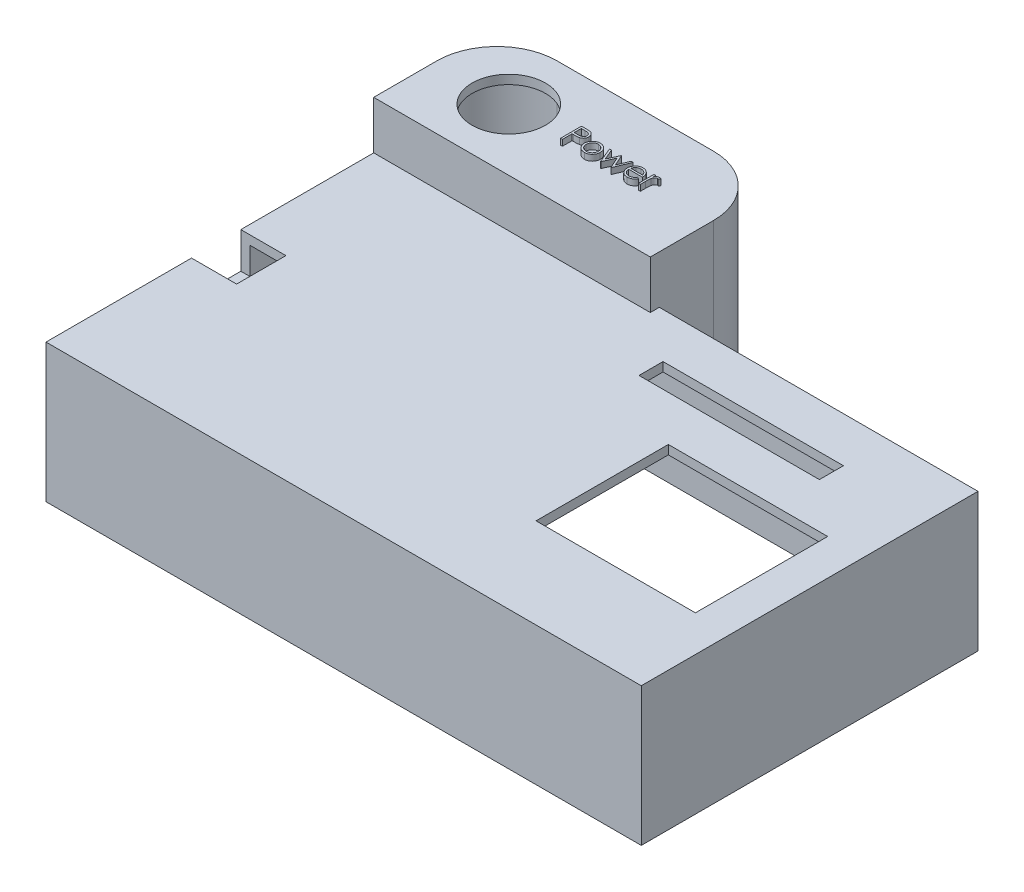
SolidWorks part; units mm, degrees
ref_plane "Front Plane" through (0, 0, 0) normal (0, 0, 1) x (1, 0, 0)
ref_plane "Top Plane" through (0, 0, 0) normal (0, 1, 0) x (1, 0, 0)
ref_plane "Right Plane" through (0, 0, 0) normal (1, 0, 0) x (0, 0, -1)
sketch "Sketch1" plane through (0, 0, 0) normal (0, 1, 0) x (1, 0, 0)
  line L1 (49.5, -28) -> (-49.5, -28)
  line L2 (49.5, -28) -> (49.5, 28)
  line L3 (49.5, 28) -> (-49.5, 28)
  line L4 (-49.5, -28) -> (-49.5, 28)
  line L5 (49.5, -28) -> (-49.5, 28) construction
  line L6 (49.5, 28) -> (-49.5, -28) construction
  point P0 (0, 0)
  dimension "D1" = 56
  dimension "D2" = 99
extrude "Boss-Extrude1" add sketch "Sketch1" along normal blind 23
sketch "Sketch3" plane through (0, 0, 0) normal (0, -1, 0) x (1, 0, 0)
  line L1 (-48, 26.5) -> (48, 26.5)
  line L2 (-48, 26.5) -> (-48, -26.5)
  line L3 (-48, -26.5) -> (48, -26.5)
  line L4 (48, 26.5) -> (48, -26.5)
  line L5 (-48, 26.5) -> (48, -26.5) construction
  line L6 (-48, -26.5) -> (48, 26.5) construction
  point P0 (0, 0)
  dimension "D1" = 96
  dimension "D2" = 53
extrude "Cut-Extrude1" cut sketch "Sketch3" against normal blind 21.5
sketch "Sketch4" plane through (0, 23, 0) normal (0, 1, 0) x (1, 0, 0)
  line L0 (-49.5, 28) -> (-49.5, -28) construction
  line L1 (-49.5, 4.4) -> (-42, 4.4)
  line L2 (-49.5, 4.4) -> (-49.5, -3.8)
  line L3 (-49.5, -3.8) -> (-42, -3.8)
  line L4 (-42, 4.4) -> (-42, -3.8)
  line L5 (49.5, 28) -> (-49.5, 28) construction
  circle A0 centre (-40.1664, 19.5284) radius 6
  dimension "D1" = 12
  dimension "D2" = 8.2
  dimension "D3" = 7.5
  dimension "D4" = 23.6
extrude "Cut-Extrude4" cut sketch "Sketch4" against normal blind 6 contours L2 L1 L4 L3
sketch "Sketch9" plane through (0, 0, 0) normal (0, -1, 0) x (1, 0, 0)
  line L0 (-48, -26.5) -> (48, -26.5) construction
  line L5 (-3.5, -26.5) -> (-49.5, -26.5)
  line L6 (-3.5, -26.5) -> (-3.5, -37)
  line L7 (-13.5, -47) -> (-39.5, -47)
  line L8 (-49.5, -26.5) -> (-49.5, -37)
  line L9 (-49.5, -28) -> (-49.5, 28) construction
  arc A0 (-39.5, -47) -> (-49.5, -37) centre (-39.5, -37) cw
  arc A1 (-3.5, -37) -> (-13.5, -47) centre (-13.5, -37) cw
  point P10 (-49.5, -47)
  point P13 (-3.5, -47)
  dimension "D4" = 10
  dimension "D1" = 20.5
  dimension "D2" = 46
  dimension "D3" = 0
extrude "Boss-Extrude5" add sketch "Sketch9" against normal blind 31
sketch "Sketch14" plane through (0, 0, 0) normal (0, -1, 0) x (-1, 0, 0)
  line L0 (3.5, 37) -> (3.5, 28) construction
  line L1 (5, 28) -> (48, 28)
  line L2 (5, 28) -> (5, 35.5)
  line L3 (15, 45.5) -> (38, 45.5)
  line L4 (48, 28) -> (48, 35.5)
  line L5 (49.5, 37) -> (49.5, -28) construction
  line L6 (39.5, 47) -> (13.5, 47) construction
  line L7 (48, 26.5) -> (-48, 26.5) construction
  arc A0 (5, 35.5) -> (15, 45.5) centre (15, 35.5) cw
  arc A1 (38, 45.5) -> (48, 35.5) centre (38, 35.5) cw
  dimension "D5" = 10
  dimension "D1" = 1.5
  dimension "D2" = 1.5
  dimension "D3" = 1.5
  dimension "D4" = 1.5
extrude "Cut-Extrude8" cut sketch "Sketch14" against normal blind 29.5
sketch "Sketch16" plane through (0, 0, -26.5) normal (0, 0, 1) x (1, 0, 0)
  line L0 (-48, 21.5) -> (48, 21.5) construction
  line L1 (-45.9875, 20) -> (-8.2349, 20)
  line L2 (-45.9875, 20) -> (-45.9875, 4)
  line L3 (-45.9875, 4) -> (-8.2349, 4)
  line L4 (-8.2349, 20) -> (-8.2349, 4)
  line L5 (-48, 0) -> (48, 0) construction
  dimension "D1" = 1.5
  dimension "D2" = 4
extrude "Cut-Extrude10" cut sketch "Sketch16" against normal blind 2
sketch "Sketch17" plane through (0, 29.5, 0) normal (0, -1, 0) x (-1, 0, 0)
  line L1 (38, 45.5) -> (15, 45.5) construction
  circle A0 centre (37.2816, 36.75) radius 6.1
  dimension "D1" = 12.2
  dimension "D2" = 8.75
extrude "Cut-Extrude11" cut sketch "Sketch17" against normal blind 2
sketch "Sketch18" plane through (0, 31, 0) normal (0, 1, 0) x (1, 0, 0)
  text T0 "Power"
extrude "Boss-Extrude6" add sketch "Sketch18" along normal blind 1
sketch "Sketch19" plane through (0, 23, 0) normal (0, 1, 0) x (1, 0, 0)
  line L2 (-49.5, -28) -> (49.5, -28) construction
  line L5 (-48, 4.4) -> (-48, -3.8) construction
  line L6 (-48, 26.5) -> (43.5, 26.5) construction
  line L7 (-48, 26.5) -> (-48, -26.5) construction
  line L8 (-48, -26.5) -> (43.5, -26.5) construction
  line L9 (43.5, 26.5) -> (43.5, -26.5) construction
  line L10 (49.5, 28) -> (-3.5, 28) construction
  line L13 (43.5, 9) -> (17, 9)
  line L14 (43.5, 9) -> (43.5, -13)
  line L15 (43.5, -13) -> (17, -13)
  line L16 (17, 9) -> (17, -13)
  dimension "D1" = 1.5
  dimension "D2" = 91.5
  dimension "D3" = 53
  dimension "D4" = 0
  dimension "D5" = 17.5
  dimension "D6" = 1.5
  dimension "D7" = 22
  dimension "D8" = 26.5
extrude "Cut-Extrude12" cut sketch "Sketch19" against normal blind 2
sketch "Sketch20" plane through (0, 23, 0) normal (0, 1, 0) x (1, 0, 0)
  line L0 (49.5, 28) -> (-3.5, 28) construction
  line L1 (4.6186, 20.5) -> (34.6186, 20.5)
  line L2 (4.6186, 20.5) -> (4.6186, 16.5)
  line L3 (4.6186, 16.5) -> (34.6186, 16.5)
  line L4 (34.6186, 20.5) -> (34.6186, 16.5)
  dimension "D1" = 4
  dimension "D2" = 7.5
  dimension "D3" = 30
extrude "Cut-Extrude13" cut sketch "Sketch20" against normal blind 2
